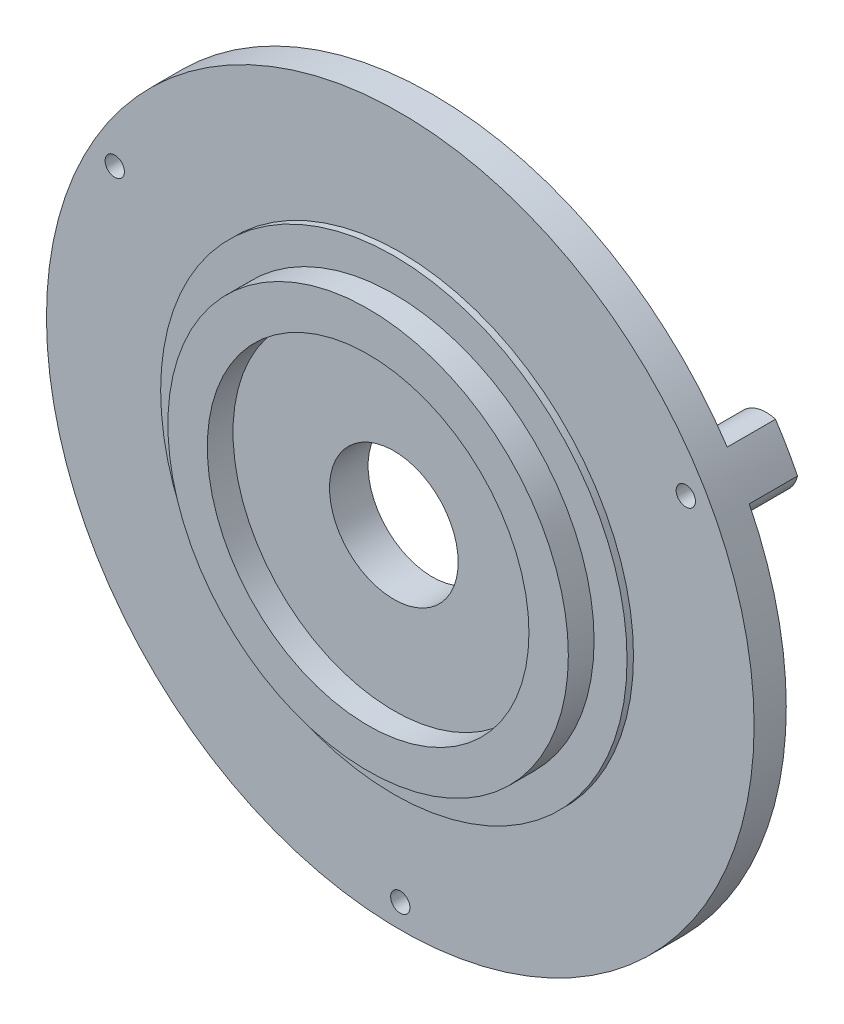
SolidWorks part; units mm, degrees
ref_plane "前视基准面" through (0, 0, 0) normal (0, 0, 1) x (1, 0, 0)
ref_plane "上视基准面" through (0, 0, 0) normal (0, 1, 0) x (1, 0, 0)
ref_plane "右视基准面" through (0, 0, 0) normal (1, 0, 0) x (0, 0, -1)
sketch "草图1" plane through (0, 0, 0) normal (0, 0, 1) x (1, 0, 0)
  circle A0 centre (0, 0) radius 22
extrude "凸台-拉伸1" add sketch "草图1" along normal blind 2
sketch "草图2" plane through (0, 0, 2) normal (0, 0, 1) x (1, 0, 0)
  circle A0 centre (0, 0) radius 12.45
  circle A1 centre (0, 0) radius 10
extrude "凸台-拉伸2" add sketch "草图2" along normal blind 2
sketch "草图3" plane through (0, 0, 2) normal (0, 0, 1) x (1, 0, 0)
  circle A0 centre (0, 0) radius 4
extrude "切除-拉伸1" cut sketch "草图3" against normal blind 11
sketch "草图4" plane through (0, 0, 0) normal (0, 0, -1) x (-1, 0, 0)
  line L0 (0, 0) -> (0, -20.5) construction
  arc A1 (1.3698, -21.9573) -> (-1.3698, -21.9573) centre (0, -20.5) ccw
  arc A2 (-19.7005, 9.7924) -> (-18.3307, 12.1649) centre (-17.7535, 10.25) ccw
  arc A3 (18.3307, 12.1649) -> (19.7005, 9.7924) centre (17.7535, 10.25) ccw
  arc A4 (-1.3698, -21.9573) -> (1.3698, -21.9573) centre (0, 0) ccw
  arc A5 (-18.3307, 12.1649) -> (-19.7005, 9.7924) centre (0, 0) ccw
  arc A6 (19.7005, 9.7924) -> (18.3307, 12.1649) centre (0, 0) ccw
  dimension "D1" = 3
  dimension "D2" = 20.5
extrude "凸台-拉伸3" add sketch "草图4" along normal blind 3
sketch "草图5" plane through (0, 0, -3) normal (0, 0, -1) x (-1, 0, 0)
  circle A1 centre (0, -20.5) radius 0.6
  circle A2 centre (-17.7535, 10.25) radius 0.6
  circle A3 centre (17.7535, 10.25) radius 0.6
extrude "切除-拉伸2" cut sketch "草图5" against normal blind 16
sketch "草图6" plane through (0, 0, 2) normal (0, 0, 1) x (1, 0, 0)
  circle A0 centre (0, 0) radius 14.5
  circle A3 centre (0, 0) radius 4
extrude "凸台-拉伸4" add sketch "草图6" along normal blind 0.4
